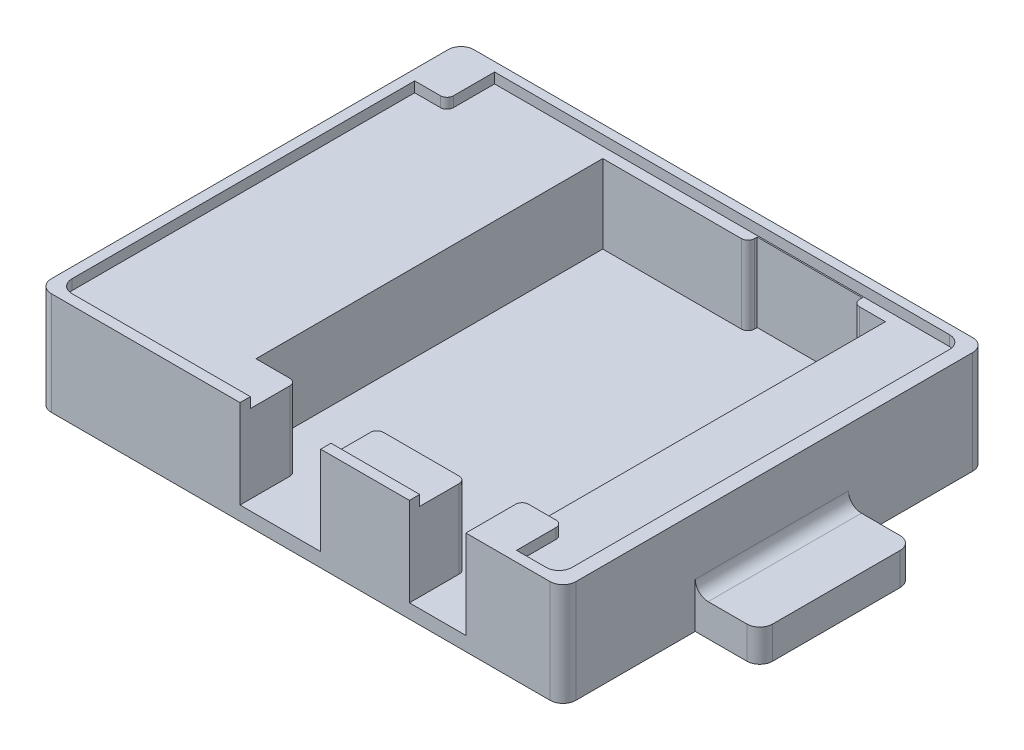
SolidWorks part; units mm, degrees
ref_plane "Front Plane" through (0, 0, 0) normal (0, 0, 1) x (1, 0, 0)
ref_plane "Top Plane" through (0, 0, 0) normal (0, 1, 0) x (1, 0, 0)
ref_plane "Right Plane" through (0, 0, 0) normal (1, 0, 0) x (0, 0, -1)
sketch "Sketch1" plane through (0, 0, 0) normal (0, 1, 0) x (1, 0, 0)
  line L1 (0, 0) -> (103.251, 0)
  line L2 (0, 0) -> (0, 83.185)
  line L3 (0, 83.185) -> (103.251, 83.185)
  line L4 (103.251, 0) -> (103.251, 83.185)
  dimension "D1" = 83.185
  dimension "D2" = 103.251
extrude "Boss-Extrude1" add sketch "Sketch1" along normal blind 20.2438
sketch "Sketch2" plane through (0, 20.2438, 0) normal (0, 1, 0) x (1, 0, 0)
  line L0 (0, 83.185) -> (0, 0) construction
  line L1 (31.75, 79.3369) -> (60.325, 79.3369)
  line L2 (31.75, 79.3369) -> (31.75, 11.0744)
  line L3 (31.75, 11.0744) -> (87.376, 11.0744)
  line L4 (87.376, 79.3369) -> (87.376, 11.0744)
  line L5 (103.251, 83.185) -> (0, 83.185) construction
  line L6 (81.026, 79.3369) -> (87.376, 79.3369)
  line L8 (60.325, 79.3369) -> (60.325, 81.153)
  line L9 (60.325, 81.153) -> (81.026, 81.153)
  line L10 (81.026, 79.3369) -> (81.026, 81.153)
  line L11 (103.251, 0) -> (103.251, 83.185) construction
  dimension "D1" = 31.75
  dimension "D2" = 3.8481
  dimension "D3" = 2.032
  dimension "D4" = 28.575
  dimension "D5" = 6.35
  dimension "D6" = 68.2625
  dimension "D7" = 15.875
extrude "Cut-Extrude1" cut sketch "Sketch2" against normal blind 17.4625
sketch "Sketch3" plane through (0, 0, 0) normal (0, 0, 1) x (1, 0, 0)
  line L0 (0, 20.2438) -> (103.251, 20.2438) construction
  line L1 (39.6875, 20.2438) -> (55.5625, 20.2438)
  line L2 (39.6875, 20.2438) -> (39.6875, 2.7813)
  line L3 (39.6875, 2.7813) -> (55.5625, 2.7813)
  line L4 (55.5625, 20.2438) -> (55.5625, 2.7813)
  line L5 (0, 20.2438) -> (0, 0) construction
  line L6 (73.025, 20.2438) -> (84.1375, 20.2438)
  line L7 (73.025, 20.2438) -> (73.025, 2.7813)
  line L8 (73.025, 2.7813) -> (84.1375, 2.7813)
  line L9 (84.1375, 20.2438) -> (84.1375, 2.7813)
  dimension "D1" = 17.4625
  dimension "D2" = 15.875
  dimension "D3" = 39.6875
  dimension "D4" = 11.1125
  dimension "D5" = 17.4625
  dimension "D6" = 17.4625
extrude "Cut-Extrude2" cut sketch "Sketch3" against normal blind 14.9225
sketch "Sketch4" plane through (0, 20.2438, 0) normal (0, 1, 0) x (1, 0, 0)
  line L0 (0, 83.185) -> (0, 0) construction
  line L1 (8.382, 81.407) -> (100.457, 81.407)
  line L2 (2.032, 72.0344) -> (2.032, 2.032)
  line L3 (2.032, 2.032) -> (84.1375, 2.032)
  line L4 (100.457, 81.407) -> (100.457, 2.032)
  line L5 (0, 0) -> (39.6875, 0) construction
  line L6 (2.032, 72.0344) -> (8.382, 72.0344)
  line L7 (8.382, 72.0344) -> (8.382, 81.407)
  line L8 (92.075, 2.032) -> (92.075, 11.0744)
  line L9 (92.075, 11.0744) -> (84.1375, 11.0744)
  line L10 (84.1375, 11.0744) -> (84.1375, 2.032)
  line L11 (84.1375, 11.0744) -> (84.1375, 0) construction
  line L12 (92.075, 2.032) -> (100.457, 2.032)
  dimension "D1" = 98.425
  dimension "D2" = 79.375
  dimension "D3" = 2.032
  dimension "D4" = 2.032
  dimension "D5" = 6.35
  dimension "D6" = 9.3726
  dimension "D7" = 7.9375
extrude "Cut-Extrude3" cut sketch "Sketch4" against normal blind 2.032
sketch "Sketch5" plane through (0, 0, 0) normal (-1, 0, 0) x (0, 0, 1)
  line L0 (-83.185, 0) -> (0, 0) construction
  line L1 (-56.1975, 0) -> (-26.035, 0)
  line L2 (-56.1975, 0) -> (-56.1975, 6.35)
  line L3 (-56.1975, 6.35) -> (-26.035, 6.35)
  line L4 (-26.035, 0) -> (-26.035, 6.35)
  line L5 (-83.185, 20.2438) -> (-83.185, 0) construction
  point P6 (-56.1975, 3.175)
  dimension "D1" = 30.1625
  dimension "D2" = 26.9875
  dimension "D3" = 6.35
extrude "Boss-Extrude2" add sketch "Sketch5" along normal blind 12.7
ref_plane "Plane1" through (51.6255, 0, 0) normal (-1, 0, 0) x (0, 0, 1)
mirror "Mirror1" about plane through (51.6255, 0, 0) normal (-1, 0, 0) of "Boss-Extrude2"
sketch "Sketch6" plane through (0, 0, -83.185) normal (0, 0, -1) x (-1, 0, 0)
  line L0 (-103.251, 0) -> (0, 0) construction
  line L1 (-66.7385, 0) -> (-36.576, 0)
  line L2 (-66.7385, 0) -> (-66.7385, 6.35)
  line L3 (-66.7385, 6.35) -> (-36.576, 6.35)
  line L4 (-36.576, 0) -> (-36.576, 6.35)
  line L5 (-103.251, 20.2438) -> (-103.251, 0) construction
  dimension "D1" = 30.1625
  dimension "D2" = 6.35
  dimension "D3" = 36.5125
extrude "Boss-Extrude3" add sketch "Sketch6" along normal blind 12.7
fillet "Fillet1" radius 2.54 10 edges at (103.251, 10.1219, 0) (115.951, 3.175, -26.035) (115.951, 3.175, -56.1975) (103.251, 10.1219, -83.185) (66.7385, 3.175, -95.885) (36.576, 3.175, -95.885) (0, 10.1219, -83.185) (-12.7, 3.175, -56.1975) (-12.7, 3.175, -26.035) (0, 10.1219, 0)
fillet "Fillet2" radius 1.27 8 edges at (39.6875, 10.4966, -11.0744) (55.5625, 10.4966, -11.0744) (73.025, 10.4966, -11.0744) (92.075, 19.2278, -11.0744) (84.1375, 11.5125, -11.0744) (81.026, 10.4966, -79.3369) (60.325, 10.4966, -79.3369) (8.382, 19.2278, -72.0344)
fillet "Fillet3" radius 2.54 3 edges at (100.457, 19.2278, -81.407) (100.457, 19.2278, -2.032) (2.032, 19.2278, -2.032)
fillet "Fillet4" radius 2.54 3 edges at (0, 6.35, -41.1163) (51.6573, 6.35, -83.185) (103.251, 6.35, -41.1163)
